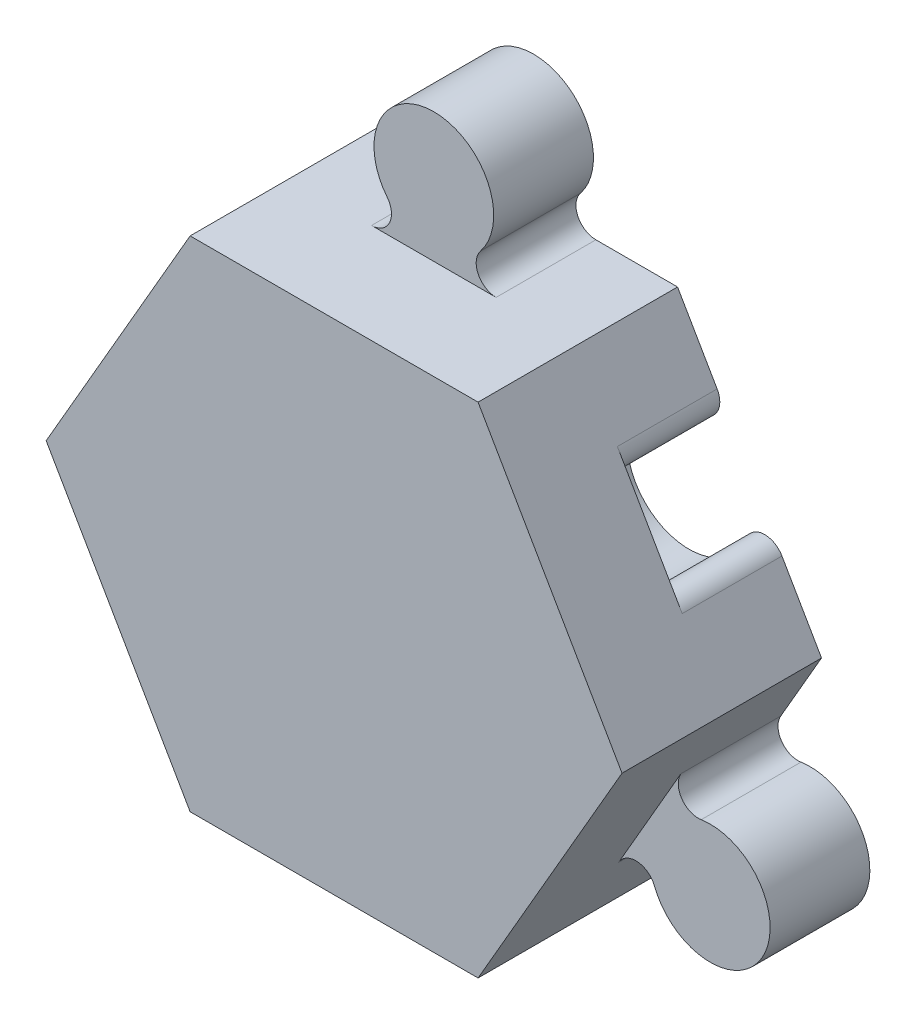
SolidWorks part; units mm, degrees
ref_plane "前视基准面" through (0, 0, 0) normal (0, 0, 1) x (1, 0, 0)
ref_plane "上视基准面" through (0, 0, 0) normal (0, 1, 0) x (1, 0, 0)
ref_plane "右视基准面" through (0, 0, 0) normal (1, 0, 0) x (0, 0, -1)
sketch "草图1" plane through (0, 0, 0) normal (0, 0, 1) x (1, 0, 0)
  line L1 (14.4338, 0) -> (7.2169, 12.5)
  line L2 (7.2169, 12.5) -> (-7.2169, 12.5)
  line L3 (-7.2169, 12.5) -> (-14.4338, 0)
  line L4 (-14.4338, 0) -> (-7.2169, -12.5)
  line L5 (-7.2169, -12.5) -> (7.2169, -12.5)
  line L6 (7.2169, -12.5) -> (14.4338, 0)
  circle A0 centre (0, 0) radius 12.5 construction
  dimension "D1" = 25
extrude "凸台-拉伸1" add sketch "草图1" along normal blind 10
sketch "草图2" plane through (0, 0, 0) normal (0, 0, -1) x (-1, 0, 0)
  line L2 (-7.2169, 12.5) -> (7.2169, 12.5) construction
  line L3 (-3.1225, 12.5) -> (3.1225, 12.5)
  line L4 (0, 19.7238) -> (0, 10.5872) construction
  arc A0 (2.3419, 14.125) -> (-2.3419, 14.125) centre (0, 16) ccw
  arc A1 (2.3419, 14.125) -> (3.1225, 12.5) centre (3.1225, 13.5) ccw
  arc A2 (-2.3419, 14.125) -> (-3.1225, 12.5) centre (-3.1225, 13.5) cw
  dimension "D1" = 6
  dimension "D2" = 2
  dimension "D3" = 3.5
extrude "凸台-拉伸2" add sketch "草图2" against normal blind 5
sketch "草图3" plane through (0, 0, 0) normal (0, 0, -1) x (-1, 0, 0)
  line L0 (-3.1225, -12.5) -> (3.1225, -12.5) construction
  line L1 (7.2169, -12.5) -> (-7.2169, -12.5) construction
  line L2 (-3.2496, -12.5) -> (0, -12.5)
  line L3 (0, 1.3937) -> (0, -16.0678) construction
  line L4 (3.2496, -12.5) -> (-3.2496, -12.5)
  arc A6 (2.3419, -10.875) -> (-2.3419, -10.875) centre (0, -9) ccw construction
  arc A7 (2.3419, -10.875) -> (3.1225, -12.5) centre (3.1225, -11.5) ccw construction
  arc A8 (-2.3419, -10.875) -> (-3.1225, -12.5) centre (-3.1225, -11.5) cw construction
  arc A9 (2.4199, -10.9375) -> (-2.457, -10.8902) centre (0, -9) ccw
  arc A10 (-3.2496, -12.5) -> (-2.457, -10.8902) centre (-3.2496, -11.5) ccw
  arc A11 (2.4199, -10.9375) -> (-2.4199, -10.9375) centre (0, -9) ccw construction
  arc A12 (3.2496, -12.5) -> (2.457, -10.8902) centre (3.2496, -11.5) cw
  dimension "D1" = 1
  dimension "D2" = 3
  dimension "D5" = 1
  dimension "D3" = 3.5
  dimension "D4" = 0.1
extrude "切除-拉伸2" cut sketch "草图3" against normal blind 5 contours A10 A12 A9 region at (0, -9.3315, 0)
ref_axis "基准轴1" through (0, 0, 0) along (0, 0, -1)
pattern_circular "阵列(圆周)1" count 3 over 360 about axis through (0, 0, 0) along (0, 0, -1) of "凸台-拉伸2", "切除-拉伸2"
